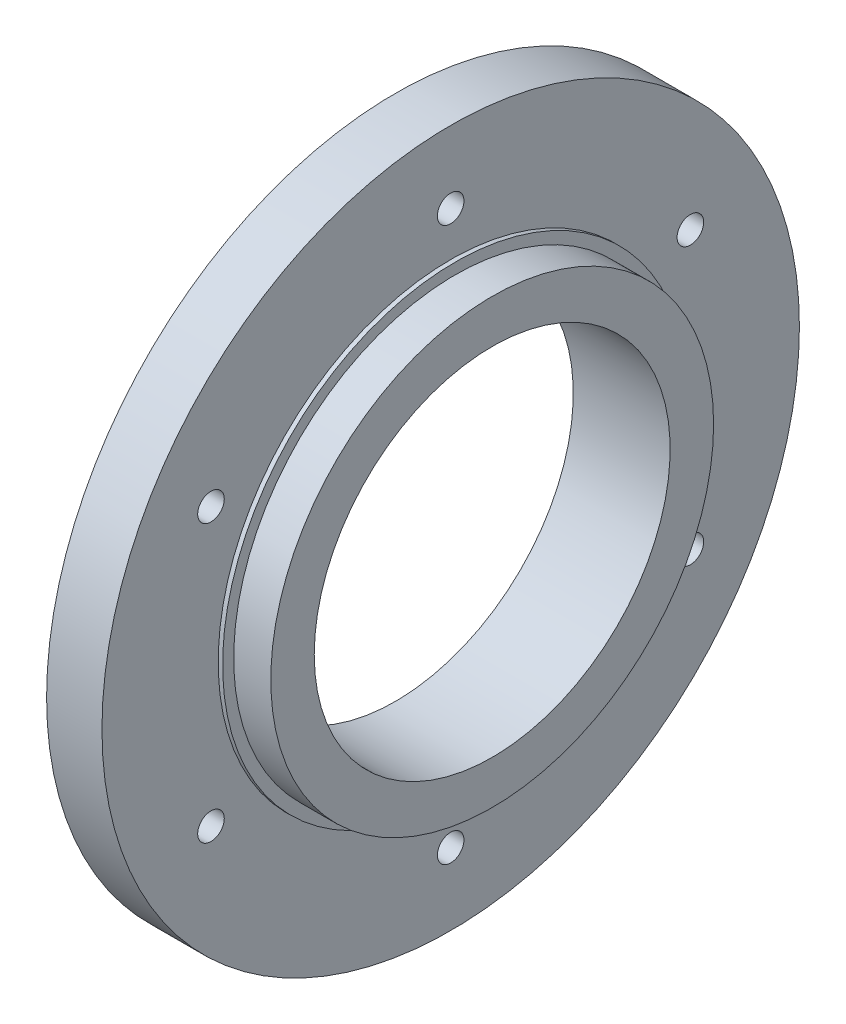
SolidWorks part; units mm, degrees
ref_plane "Ebene vorne" through (0, 0, 0) normal (0, 0, 1) x (1, 0, 0)
ref_plane "Ebene oben" through (0, 0, 0) normal (0, 1, 0) x (1, 0, 0)
ref_plane "Ebene rechts" through (0, 0, 0) normal (1, 0, 0) x (0, 0, -1)
sketch "Skizze1" plane through (0, 0, 0) normal (0, 0, 1) x (1, 0, 0)
  line L0 (0, 0) -> (-40471.317, 0) construction
  line L1 (0, 0) -> (0, 31.5)
  line L2 (0, 31.5) -> (5, 31.5)
  line L3 (5, 31.5) -> (5, 21)
  line L4 (5, 21) -> (5.4, 21)
  line L6 (8.75, 0) -> (0, 0)
  line L7 (8.75, 0) -> (8.75, 20)
  line L8 (8.75, 20) -> (5.4, 20)
  line L9 (5.4, 21) -> (5.4, 20)
  dimension "D1" = 42
  dimension "D2" = 0.4
  dimension "D3" = 3.35
  dimension "D4" = 63
  dimension "D5" = 40
  dimension "D6" = 8.75
revolve "Rotation1" add sketch "Skizze1" angle 360 about L0
sketch "Skizze2" plane through (0, 0, 0) normal (-1, 0, 0) x (0, 0, 1)
  circle A0 centre (0, 0) radius 16.075
  dimension "D1" = 32.15
extrude "Schnitt-Linear austragen1" cut sketch "Skizze2" against normal through all
sketch "Skizze3" plane through (5, 0, 0) normal (1, 0, 0) x (0, 0, -1)
  line L0 (0, 0) -> (0, -50000) construction
  line L2 (1.7321, 22) -> (3.4641, 25)
  line L3 (3.4641, 25) -> (1.7321, 28)
  line L4 (1.7321, 28) -> (-1.7321, 28)
  line L5 (-1.7321, 28) -> (-3.4641, 25)
  line L6 (-3.4641, 25) -> (-1.7321, 22)
  line L7 (-1.7321, 22) -> (1.7321, 22)
  circle A0 centre (0, 25) radius 3 construction
  circle A1 centre (0, 0) radius 25 construction
  dimension "D2" = 50
  dimension "D1" = 6
hole_wizard "Ø2.4 (2.4) Durchmesser Bohrung1" positions "Skizze4" profile "Skizze5" hole size "Ø2.4" standard "ISO" end condition through all
sketch "Skizze4" plane through (5, 0, 0) normal (1, 0, 0) x (0, 0, -1)
  line L0 (0, 0) -> (0, -50000) construction
  circle A0 centre (0, 0) radius 25 construction
  point P9 (0, 25)
  dimension "D1" = 50
sketch "Skizze5" plane through (5, 25, 0) normal (0, 1, 0) x (0, 0, -1)
  line L0 (0, 0) -> (0, 5)
  line L1 (0, 5) -> (1.2, 5)
  line L2 (1.2, 5) -> (1.2, 0)
  line L5 (1.2, 0) -> (0, 0)
  line L11 (0, -6.35) -> (0, 107.95) construction
  dimension "Bohrerdurchmesser" = 2.4
  dimension "Bohrungstiefe" = 5
pattern_circular "Kreismuster2" count 6 over 360 about axis through (8.75, 0, 0) along (-1, 0, 0) of "Ø2.4 (2.4) Durchmesser Bohrung1"
